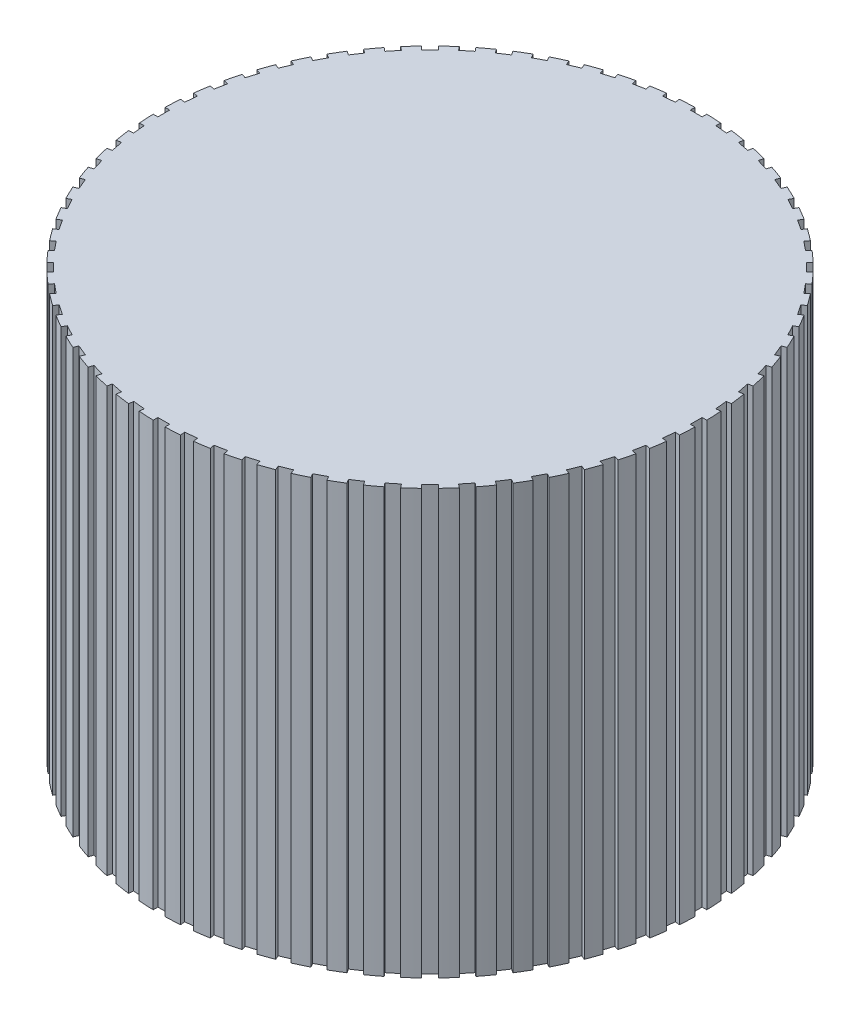
SolidWorks part; units mm, degrees
material "ABS"
ref_plane "Front Plane" through (0, 0, 0) normal (0, 0, 1) x (1, 0, 0)
ref_plane "Top Plane" through (0, 0, 0) normal (0, 1, 0) x (1, 0, 0)
ref_plane "Right Plane" through (0, 0, 0) normal (1, 0, 0) x (0, 0, -1)
sketch "Sketch1" plane through (0, 0, 0) normal (0, 1, 0) x (1, 0, 0)
  circle A0 centre (0, 0) radius 5.75
  circle A1 centre (0, 0) radius 2.375
  dimension "D1" = 11.5
  dimension "D2" = 4.75
extrude "Boss-Extrude1" add sketch "Sketch1" along normal blind 5 contours A1 | A0 A1 region at (-5.5874, 0, 0) region at (0, 0, 0)
extrude "Boss-Extrude2" add sketch "Sketch1<3>" against normal blind 4 contours A0 A1 region at (-5.5874, 0, 0)
sketch "Sketch1<3>" plane through (0, 0, 0) normal (0, 1, 0) x (1, 0, 0) same geometry as "Sketch1"
sketch "Sketch2" plane through (0, -4, 0) normal (0, -1, 0) x (1, 0, 0)
  line L0 (0.4784, 6.1326) -> (0.4294, 5.635)
  line L1 (-0.125, 6.15) -> (0.125, 6.15)
  line L2 (-0.125, 6.15) -> (-0.125, 5.65)
  line L3 (-0.125, 5.65) -> (0.125, 5.65)
  line L4 (0.125, 6.15) -> (0.125, 5.65)
  line L5 (0.4784, 6.1326) -> (0.7272, 6.1081)
  line L6 (0.7272, 6.1081) -> (0.6782, 5.6105)
  line L7 (0.4294, 5.635) -> (0.6782, 5.6105)
  line L8 (1.0772, 6.0562) -> (0.9797, 5.5658)
  line L9 (1.0772, 6.0562) -> (1.3224, 6.0074)
  line L10 (1.3224, 6.0074) -> (1.2249, 5.5171)
  line L11 (0.9797, 5.5658) -> (1.2249, 5.5171)
  line L12 (1.6656, 5.9215) -> (1.5205, 5.443)
  line L13 (1.6656, 5.9215) -> (1.9049, 5.8489)
  line L14 (1.9049, 5.8489) -> (1.7597, 5.3704)
  line L15 (1.5205, 5.443) -> (1.7597, 5.3704)
  line L16 (2.238, 5.7297) -> (2.0467, 5.2678)
  line L17 (2.238, 5.7297) -> (2.469, 5.634)
  line L18 (2.469, 5.634) -> (2.2776, 5.1721)
  line L19 (2.0467, 5.2678) -> (2.2776, 5.1721)
  line L20 (2.7888, 5.4827) -> (2.5532, 5.0418)
  line L21 (2.7888, 5.4827) -> (3.0093, 5.3649)
  line L22 (3.0093, 5.3649) -> (2.7736, 4.9239)
  line L23 (2.5532, 5.0418) -> (2.7736, 4.9239)
  line L24 (3.3128, 5.183) -> (3.035, 4.7672)
  line L25 (3.3128, 5.183) -> (3.5207, 5.0441)
  line L26 (3.5207, 5.0441) -> (3.2429, 4.6284)
  line L27 (3.035, 4.7672) -> (3.2429, 4.6284)
  line L28 (3.8049, 4.8333) -> (3.4877, 4.4468)
  line L29 (3.8049, 4.8333) -> (3.9981, 4.6747)
  line L30 (3.9981, 4.6747) -> (3.6809, 4.2882)
  line L31 (3.4877, 4.4468) -> (3.6809, 4.2882)
  line L32 (4.2603, 4.4371) -> (3.9068, 4.0835)
  line L33 (4.2603, 4.4371) -> (4.4371, 4.2603)
  line L34 (4.4371, 4.2603) -> (4.0835, 3.9068)
  line L35 (3.9068, 4.0835) -> (4.0835, 3.9068)
  line L36 (4.6747, 3.9981) -> (4.2882, 3.6809)
  line L37 (4.6747, 3.9981) -> (4.8333, 3.8049)
  line L38 (4.8333, 3.8049) -> (4.4468, 3.4877)
  line L39 (4.2882, 3.6809) -> (4.4468, 3.4877)
  line L40 (5.0441, 3.5207) -> (4.6284, 3.2429)
  line L41 (5.0441, 3.5207) -> (5.183, 3.3128)
  line L42 (5.183, 3.3128) -> (4.7672, 3.035)
  line L43 (4.6284, 3.2429) -> (4.7672, 3.035)
  line L44 (5.3649, 3.0093) -> (4.9239, 2.7736)
  line L45 (5.3649, 3.0093) -> (5.4827, 2.7888)
  line L46 (5.4827, 2.7888) -> (5.0418, 2.5532)
  line L47 (4.9239, 2.7736) -> (5.0418, 2.5532)
  line L48 (5.634, 2.469) -> (5.1721, 2.2776)
  line L49 (5.634, 2.469) -> (5.7297, 2.238)
  line L50 (5.7297, 2.238) -> (5.2678, 2.0467)
  line L51 (5.1721, 2.2776) -> (5.2678, 2.0467)
  line L52 (5.8489, 1.9049) -> (5.3704, 1.7597)
  line L53 (5.8489, 1.9049) -> (5.9215, 1.6656)
  line L54 (5.9215, 1.6656) -> (5.443, 1.5205)
  line L55 (5.3704, 1.7597) -> (5.443, 1.5205)
  line L56 (6.0074, 1.3224) -> (5.5171, 1.2249)
  line L57 (6.0074, 1.3224) -> (6.0562, 1.0772)
  line L58 (6.0562, 1.0772) -> (5.5658, 0.9797)
  line L59 (5.5171, 1.2249) -> (5.5658, 0.9797)
  line L60 (6.1081, 0.7272) -> (5.6105, 0.6782)
  line L61 (6.1081, 0.7272) -> (6.1326, 0.4784)
  line L62 (6.1326, 0.4784) -> (5.635, 0.4294)
  line L63 (5.6105, 0.6782) -> (5.635, 0.4294)
  line L64 (6.15, 0.125) -> (5.65, 0.125)
  line L65 (6.15, 0.125) -> (6.15, -0.125)
  line L66 (6.15, -0.125) -> (5.65, -0.125)
  line L67 (5.65, 0.125) -> (5.65, -0.125)
  line L68 (6.1326, -0.4784) -> (5.635, -0.4294)
  line L69 (6.1326, -0.4784) -> (6.1081, -0.7272)
  line L70 (6.1081, -0.7272) -> (5.6105, -0.6782)
  line L71 (5.635, -0.4294) -> (5.6105, -0.6782)
  line L72 (6.0562, -1.0772) -> (5.5658, -0.9797)
  line L73 (6.0562, -1.0772) -> (6.0074, -1.3224)
  line L74 (6.0074, -1.3224) -> (5.5171, -1.2249)
  line L75 (5.5658, -0.9797) -> (5.5171, -1.2249)
  line L76 (5.9215, -1.6656) -> (5.443, -1.5205)
  line L77 (5.9215, -1.6656) -> (5.8489, -1.9049)
  line L78 (5.8489, -1.9049) -> (5.3704, -1.7597)
  line L79 (5.443, -1.5205) -> (5.3704, -1.7597)
  line L80 (5.7297, -2.238) -> (5.2678, -2.0467)
  line L81 (5.7297, -2.238) -> (5.634, -2.469)
  line L82 (5.634, -2.469) -> (5.1721, -2.2776)
  line L83 (5.2678, -2.0467) -> (5.1721, -2.2776)
  line L84 (5.4827, -2.7888) -> (5.0418, -2.5532)
  line L85 (5.4827, -2.7888) -> (5.3649, -3.0093)
  line L86 (5.3649, -3.0093) -> (4.9239, -2.7736)
  line L87 (5.0418, -2.5532) -> (4.9239, -2.7736)
  line L88 (5.183, -3.3128) -> (4.7672, -3.035)
  line L89 (5.183, -3.3128) -> (5.0441, -3.5207)
  line L90 (5.0441, -3.5207) -> (4.6284, -3.2429)
  line L91 (4.7672, -3.035) -> (4.6284, -3.2429)
  line L92 (4.8333, -3.8049) -> (4.4468, -3.4877)
  line L93 (4.8333, -3.8049) -> (4.6747, -3.9981)
  line L94 (4.6747, -3.9981) -> (4.2882, -3.6809)
  line L95 (4.4468, -3.4877) -> (4.2882, -3.6809)
  line L96 (4.4371, -4.2603) -> (4.0835, -3.9068)
  line L97 (4.4371, -4.2603) -> (4.2603, -4.4371)
  line L98 (4.2603, -4.4371) -> (3.9068, -4.0835)
  line L99 (4.0835, -3.9068) -> (3.9068, -4.0835)
  line L100 (3.9981, -4.6747) -> (3.6809, -4.2882)
  line L101 (3.9981, -4.6747) -> (3.8049, -4.8333)
  line L102 (3.8049, -4.8333) -> (3.4877, -4.4468)
  line L103 (3.6809, -4.2882) -> (3.4877, -4.4468)
  line L104 (3.5207, -5.0441) -> (3.2429, -4.6284)
  line L105 (3.5207, -5.0441) -> (3.3128, -5.183)
  line L106 (3.3128, -5.183) -> (3.035, -4.7672)
  line L107 (3.2429, -4.6284) -> (3.035, -4.7672)
  line L108 (3.0093, -5.3649) -> (2.7736, -4.9239)
  line L109 (3.0093, -5.3649) -> (2.7888, -5.4827)
  line L110 (2.7888, -5.4827) -> (2.5532, -5.0418)
  line L111 (2.7736, -4.9239) -> (2.5532, -5.0418)
  line L112 (2.469, -5.634) -> (2.2776, -5.1721)
  line L113 (2.469, -5.634) -> (2.238, -5.7297)
  line L114 (2.238, -5.7297) -> (2.0467, -5.2678)
  line L115 (2.2776, -5.1721) -> (2.0467, -5.2678)
  line L116 (1.9049, -5.8489) -> (1.7597, -5.3704)
  line L117 (1.9049, -5.8489) -> (1.6656, -5.9215)
  line L118 (1.6656, -5.9215) -> (1.5205, -5.443)
  line L119 (1.7597, -5.3704) -> (1.5205, -5.443)
  line L120 (1.3224, -6.0074) -> (1.2249, -5.5171)
  line L121 (1.3224, -6.0074) -> (1.0772, -6.0562)
  line L122 (1.0772, -6.0562) -> (0.9797, -5.5658)
  line L123 (1.2249, -5.5171) -> (0.9797, -5.5658)
  line L124 (0.7272, -6.1081) -> (0.6782, -5.6105)
  line L125 (0.7272, -6.1081) -> (0.4784, -6.1326)
  line L126 (0.4784, -6.1326) -> (0.4294, -5.635)
  line L127 (0.6782, -5.6105) -> (0.4294, -5.635)
  line L128 (0.125, -6.15) -> (0.125, -5.65)
  line L129 (0.125, -6.15) -> (-0.125, -6.15)
  line L130 (-0.125, -6.15) -> (-0.125, -5.65)
  line L131 (0.125, -5.65) -> (-0.125, -5.65)
  line L132 (-0.4784, -6.1326) -> (-0.4294, -5.635)
  line L133 (-0.4784, -6.1326) -> (-0.7272, -6.1081)
  line L134 (-0.7272, -6.1081) -> (-0.6782, -5.6105)
  line L135 (-0.4294, -5.635) -> (-0.6782, -5.6105)
  line L136 (-1.0772, -6.0562) -> (-0.9797, -5.5658)
  line L137 (-1.0772, -6.0562) -> (-1.3224, -6.0074)
  line L138 (-1.3224, -6.0074) -> (-1.2249, -5.5171)
  line L139 (-0.9797, -5.5658) -> (-1.2249, -5.5171)
  line L140 (-1.6656, -5.9215) -> (-1.5205, -5.443)
  line L141 (-1.6656, -5.9215) -> (-1.9049, -5.8489)
  line L142 (-1.9049, -5.8489) -> (-1.7597, -5.3704)
  line L143 (-1.5205, -5.443) -> (-1.7597, -5.3704)
  line L144 (-2.238, -5.7297) -> (-2.0467, -5.2678)
  line L145 (-2.238, -5.7297) -> (-2.469, -5.634)
  line L146 (-2.469, -5.634) -> (-2.2776, -5.1721)
  line L147 (-2.0467, -5.2678) -> (-2.2776, -5.1721)
  line L148 (-2.7888, -5.4827) -> (-2.5532, -5.0418)
  line L149 (-2.7888, -5.4827) -> (-3.0093, -5.3649)
  line L150 (-3.0093, -5.3649) -> (-2.7736, -4.9239)
  line L151 (-2.5532, -5.0418) -> (-2.7736, -4.9239)
  line L152 (-3.3128, -5.183) -> (-3.035, -4.7672)
  line L153 (-3.3128, -5.183) -> (-3.5207, -5.0441)
  line L154 (-3.5207, -5.0441) -> (-3.2429, -4.6284)
  line L155 (-3.035, -4.7672) -> (-3.2429, -4.6284)
  line L156 (-3.8049, -4.8333) -> (-3.4877, -4.4468)
  line L157 (-3.8049, -4.8333) -> (-3.9981, -4.6747)
  line L158 (-3.9981, -4.6747) -> (-3.6809, -4.2882)
  line L159 (-3.4877, -4.4468) -> (-3.6809, -4.2882)
  line L160 (-4.2603, -4.4371) -> (-3.9068, -4.0835)
  line L161 (-4.2603, -4.4371) -> (-4.4371, -4.2603)
  line L162 (-4.4371, -4.2603) -> (-4.0835, -3.9068)
  line L163 (-3.9068, -4.0835) -> (-4.0835, -3.9068)
  line L164 (-4.6747, -3.9981) -> (-4.2882, -3.6809)
  line L165 (-4.6747, -3.9981) -> (-4.8333, -3.8049)
  line L166 (-4.8333, -3.8049) -> (-4.4468, -3.4877)
  line L167 (-4.2882, -3.6809) -> (-4.4468, -3.4877)
  line L168 (-5.0441, -3.5207) -> (-4.6284, -3.2429)
  line L169 (-5.0441, -3.5207) -> (-5.183, -3.3128)
  line L170 (-5.183, -3.3128) -> (-4.7672, -3.035)
  line L171 (-4.6284, -3.2429) -> (-4.7672, -3.035)
  line L172 (-5.3649, -3.0093) -> (-4.9239, -2.7736)
  line L173 (-5.3649, -3.0093) -> (-5.4827, -2.7888)
  line L174 (-5.4827, -2.7888) -> (-5.0418, -2.5532)
  line L175 (-4.9239, -2.7736) -> (-5.0418, -2.5532)
  line L176 (-5.634, -2.469) -> (-5.1721, -2.2776)
  line L177 (-5.634, -2.469) -> (-5.7297, -2.238)
  line L178 (-5.7297, -2.238) -> (-5.2678, -2.0467)
  line L179 (-5.1721, -2.2776) -> (-5.2678, -2.0467)
  line L180 (-5.8489, -1.9049) -> (-5.3704, -1.7597)
  line L181 (-5.8489, -1.9049) -> (-5.9215, -1.6656)
  line L182 (-5.9215, -1.6656) -> (-5.443, -1.5205)
  line L183 (-5.3704, -1.7597) -> (-5.443, -1.5205)
  line L184 (-6.0074, -1.3224) -> (-5.5171, -1.2249)
  line L185 (-6.0074, -1.3224) -> (-6.0562, -1.0772)
  line L186 (-6.0562, -1.0772) -> (-5.5658, -0.9797)
  line L187 (-5.5171, -1.2249) -> (-5.5658, -0.9797)
  line L188 (-6.1081, -0.7272) -> (-5.6105, -0.6782)
  line L189 (-6.1081, -0.7272) -> (-6.1326, -0.4784)
  line L190 (-6.1326, -0.4784) -> (-5.635, -0.4294)
  line L191 (-5.6105, -0.6782) -> (-5.635, -0.4294)
  line L192 (-6.15, -0.125) -> (-5.65, -0.125)
  line L193 (-6.15, -0.125) -> (-6.15, 0.125)
  line L194 (-6.15, 0.125) -> (-5.65, 0.125)
  line L195 (-5.65, -0.125) -> (-5.65, 0.125)
  line L196 (-6.1326, 0.4784) -> (-5.635, 0.4294)
  line L197 (-6.1326, 0.4784) -> (-6.1081, 0.7272)
  line L198 (-6.1081, 0.7272) -> (-5.6105, 0.6782)
  line L199 (-5.635, 0.4294) -> (-5.6105, 0.6782)
  line L200 (-6.0562, 1.0772) -> (-5.5658, 0.9797)
  line L201 (-6.0562, 1.0772) -> (-6.0074, 1.3224)
  line L202 (-6.0074, 1.3224) -> (-5.5171, 1.2249)
  line L203 (-5.5658, 0.9797) -> (-5.5171, 1.2249)
  line L204 (-5.9215, 1.6656) -> (-5.443, 1.5205)
  line L205 (-5.9215, 1.6656) -> (-5.8489, 1.9049)
  line L206 (-5.8489, 1.9049) -> (-5.3704, 1.7597)
  line L207 (-5.443, 1.5205) -> (-5.3704, 1.7597)
  line L208 (-5.7297, 2.238) -> (-5.2678, 2.0467)
  line L209 (-5.7297, 2.238) -> (-5.634, 2.469)
  line L210 (-5.634, 2.469) -> (-5.1721, 2.2776)
  line L211 (-5.2678, 2.0467) -> (-5.1721, 2.2776)
  line L212 (-5.4827, 2.7888) -> (-5.0418, 2.5532)
  line L213 (-5.4827, 2.7888) -> (-5.3649, 3.0093)
  line L214 (-5.3649, 3.0093) -> (-4.9239, 2.7736)
  line L215 (-5.0418, 2.5532) -> (-4.9239, 2.7736)
  line L216 (-5.183, 3.3128) -> (-4.7672, 3.035)
  line L217 (-5.183, 3.3128) -> (-5.0441, 3.5207)
  line L218 (-5.0441, 3.5207) -> (-4.6284, 3.2429)
  line L219 (-4.7672, 3.035) -> (-4.6284, 3.2429)
  line L220 (-4.8333, 3.8049) -> (-4.4468, 3.4877)
  line L221 (-4.8333, 3.8049) -> (-4.6747, 3.9981)
  line L222 (-4.6747, 3.9981) -> (-4.2882, 3.6809)
  line L223 (-4.4468, 3.4877) -> (-4.2882, 3.6809)
  line L224 (-4.4371, 4.2603) -> (-4.0835, 3.9068)
  line L225 (-4.4371, 4.2603) -> (-4.2603, 4.4371)
  line L226 (-4.2603, 4.4371) -> (-3.9068, 4.0835)
  line L227 (-4.0835, 3.9068) -> (-3.9068, 4.0835)
  line L228 (-3.9981, 4.6747) -> (-3.6809, 4.2882)
  line L229 (-3.9981, 4.6747) -> (-3.8049, 4.8333)
  line L230 (-3.8049, 4.8333) -> (-3.4877, 4.4468)
  line L231 (-3.6809, 4.2882) -> (-3.4877, 4.4468)
  line L232 (-3.5207, 5.0441) -> (-3.2429, 4.6284)
  line L233 (-3.5207, 5.0441) -> (-3.3128, 5.183)
  line L234 (-3.3128, 5.183) -> (-3.035, 4.7672)
  line L235 (-3.2429, 4.6284) -> (-3.035, 4.7672)
  line L236 (-3.0093, 5.3649) -> (-2.7736, 4.9239)
  line L237 (-3.0093, 5.3649) -> (-2.7888, 5.4827)
  line L238 (-2.7888, 5.4827) -> (-2.5532, 5.0418)
  line L239 (-2.7736, 4.9239) -> (-2.5532, 5.0418)
  line L240 (-2.469, 5.634) -> (-2.2776, 5.1721)
  line L241 (-2.469, 5.634) -> (-2.238, 5.7297)
  line L242 (-2.238, 5.7297) -> (-2.0467, 5.2678)
  line L243 (-2.2776, 5.1721) -> (-2.0467, 5.2678)
  line L244 (-1.9049, 5.8489) -> (-1.7597, 5.3704)
  line L245 (-1.9049, 5.8489) -> (-1.6656, 5.9215)
  line L246 (-1.6656, 5.9215) -> (-1.5205, 5.443)
  line L247 (-1.7597, 5.3704) -> (-1.5205, 5.443)
  line L248 (-1.3224, 6.0074) -> (-1.2249, 5.5171)
  line L249 (-1.3224, 6.0074) -> (-1.0772, 6.0562)
  line L250 (-1.0772, 6.0562) -> (-0.9797, 5.5658)
  line L251 (-1.2249, 5.5171) -> (-0.9797, 5.5658)
  line L252 (-0.7272, 6.1081) -> (-0.6782, 5.6105)
  line L253 (-0.7272, 6.1081) -> (-0.4784, 6.1326)
  line L254 (-0.4784, 6.1326) -> (-0.4294, 5.635)
  line L255 (-0.6782, 5.6105) -> (-0.4294, 5.635)
  point P4 (0, 6.15)
  point P260 (0, 0)
  dimension "D1" = 5.65
  dimension "D2" = 0.25
  dimension "D3" = 0.5
  dimension "D4" = 64
extrude "Cut-Extrude1" cut sketch "Sketch2" against normal through all
